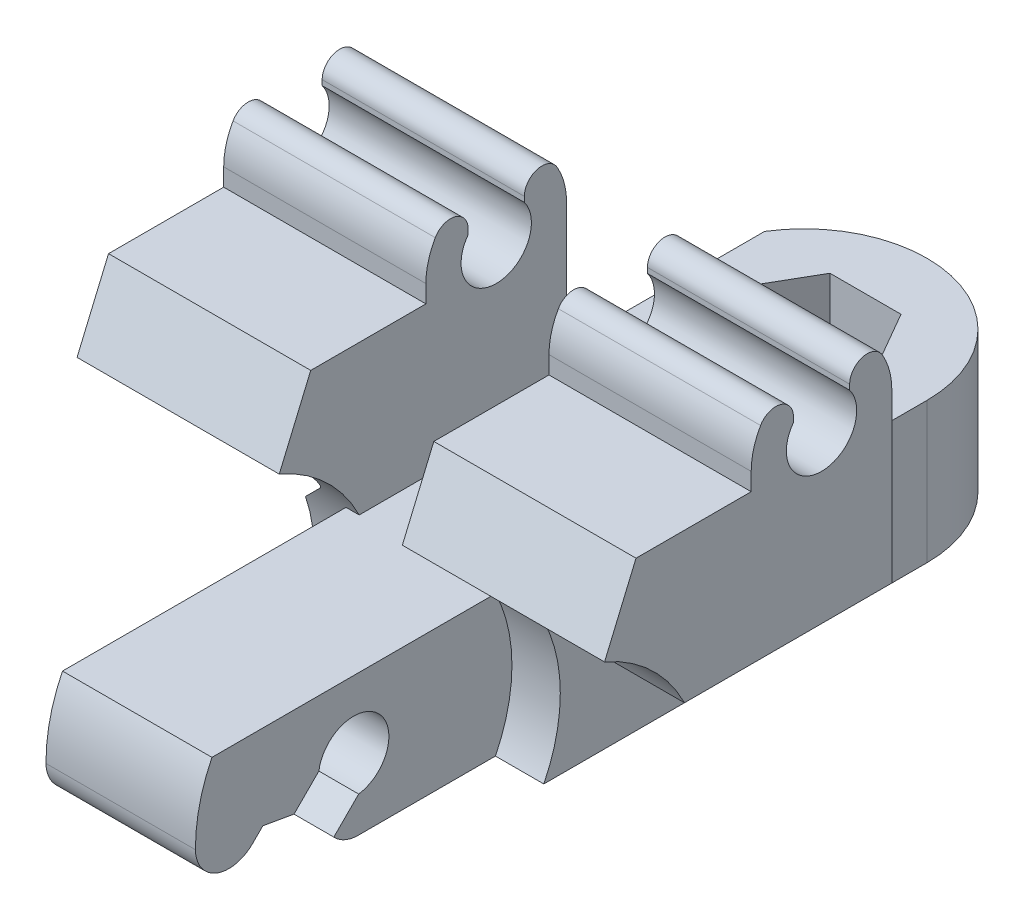
SolidWorks part; units mm, degrees
ref_plane "Front Plane" through (0, 0, 0) normal (0, 0, 1) x (1, 0, 0)
ref_plane "Top Plane" through (0, 0, 0) normal (0, 1, 0) x (1, 0, 0)
ref_plane "Right Plane" through (0, 0, 0) normal (1, 0, 0) x (0, 0, -1)
sketch "Sketch3" plane through (0, 0, 0) normal (1, 0, 0) x (0, 0, -1)
  line L0 (0.2828, -1.9799) -> (-1.9799, 0.2828)
  line L1 (0.2828, -1.9799) -> (-1.1314, -3.3941)
  line L2 (-1.1314, -3.3941) -> (-0.8188, -5.1668)
  line L3 (-0.8188, -5.1668) -> (-3.8071, -8.1551)
  line L4 (-1.9799, 0.2828) -> (-3.3941, -1.1314)
  line L5 (-3.3941, -1.1314) -> (-5.1668, -0.8188)
  line L6 (-5.1668, -0.8188) -> (-8.1551, -3.8071)
  line L7 (-0.8485, -0.8485) -> (0, 0) construction
  line L8 (0, 0) -> (-2, 0) construction
  line L9 (-1.9799, 0.2828) -> (-5.1668, -0.8188) construction
  line L10 (-0.8188, -5.1668) -> (0.2828, -1.9799) construction
  circle A0 centre (0, 0) radius 2
  circle A1 centre (0, 0) radius 8.5 construction
  circle A2 centre (0, 0) radius 9 construction
  circle A3 centre (0, 0) radius 9
  dimension "D1" = 4
  dimension "D2" = 17
  dimension "D3" = 7
  dimension "D4" = 0.5
  dimension "D5" = 2
  dimension "D7" = 3.2
  dimension "D6" = 1.8
  dimension "D8" = 45
  dimension "D9" = 125
extrude "Boss-Extrude1" add sketch "Sketch3" along normal mid plane 8.5 contours A3 L6 L5 L4 A0 L1 L2 L3 | A3 region at (0, -1.4772, -1.7032)
sketch "Sketch5" plane through (0, 0, 0) normal (1, 0, 0) x (0, 0, -1)
  line L0 (0, 9) -> (29.856, 9)
  line L1 (29.856, 9) -> (29.856, -9)
  line L2 (29.856, -9) -> (0, -9)
  arc A0 (-3.8071, -8.1551) -> (-8.1551, -3.8071) centre (0, 0) ccw construction
  arc A1 (0, -9) -> (0, 9) centre (0, 0) ccw
  dimension "D1" = 29.856
extrude "Boss-Extrude2" add sketch "Sketch5" along normal mid plane 14
sketch "Sketch6" plane through (0, 9, 0) normal (0, 1, 0) x (1, 0, 0)
  line L0 (7, 29.856) -> (-7, 29.856) construction
  circle A0 centre (0, 29.856) radius 7
extrude "Boss-Extrude3" add sketch "Sketch6" against normal up to surface (18 mm away) up to face at (0, -9, -9.952)
sketch "Sketch7" plane through (0, 0, 0) normal (0, 1, 0) x (1, 0, 0)
  circle A0 centre (0, 29.856) radius 4.5
  dimension "D1" = 9
extrude "Boss-Extrude4" add sketch "Sketch7" along normal blind 8 and the other way blind 8
sketch "Sketch8" plane through (0, 9, 0) normal (0, 1, 0) x (1, 0, 0)
  line L0 (4.25, -9) -> (4.25, 0) construction
  line L1 (-4.25, 0) -> (-4.25, -9) construction
  line L3 (7, 0) -> (7, 29.856) construction
  line L4 (-7, 29.856) -> (-7, 0) construction
  line L5 (-7, 0) -> (-4.25, 0) construction
  line L6 (4.25, 0) -> (7, 0) construction
  line L7 (4.25, -9) -> (4.25, 0)
  line L8 (-4.25, 0) -> (-4.25, -9)
  line L9 (-4.25, -9) -> (4.25, -9)
  line L10 (7, 0) -> (7, 29.856)
  line L11 (-7, 29.856) -> (-7, 0)
  line L12 (-7, 0) -> (-4.25, 0)
  line L13 (4.25, 0) -> (7, 0)
  arc A0 (7, 29.856) -> (-7, 29.856) centre (0, 29.856) ccw construction
  arc A1 (7, 29.856) -> (-7, 29.856) centre (0, 29.856) ccw
  line M10 (7, 0) -> (7, 29.856)
  arc M11 (7, 29.856) -> (-7, 29.856) centre (0, 29.856) ccw
  line M12 (-7, 29.856) -> (-7, 0)
  line M13 (-7, 0) -> (-4.25, 0)
  line M14 (-4.25, 0) -> (4.25, 0)
  line M15 (4.25, 0) -> (7, 0)
extrude "Cut-Extrude2" cut sketch "Sketch8" against normal offset from surface (5 mm away) 4 contours M15 M10 M11 M12 M13 M14 | L8 L9 L7 M14 region at (0, 9, 4.5) region at (0, 9, -17.7114) up to plane "Top Plane"
sketch "Sketch9" plane through (0, -9, 0) normal (0, -1, 0) x (1, 0, 0)
  line L7 (4.25, 0) -> (4.25, 9)
  line L8 (7, 0) -> (4.25, 0)
  line L9 (7, -29.856) -> (7, 0)
  line L10 (-7, 0) -> (-7, -29.856)
  line L11 (-4.25, 0) -> (-7, 0)
  line L12 (-4.25, 9) -> (-4.25, 0)
  line L13 (4.25, 9) -> (-4.25, 9)
  line L14 (4.25, 0) -> (4.25, 9)
  line L15 (7, 0) -> (4.25, 0)
  line L16 (7, -29.856) -> (7, 0)
  line L17 (-7, 0) -> (-7, -29.856)
  line L18 (-4.25, 0) -> (-7, 0)
  line L19 (-4.25, 9) -> (-4.25, 0)
  line L20 (4.25, 9) -> (-4.25, 9)
  arc A1 (-7, -29.856) -> (7, -29.856) centre (0, -29.856) ccw
  arc A2 (-7, -29.856) -> (7, -29.856) centre (0, -29.856) ccw
  line M10 (-7, 0) -> (-7, -29.856)
  arc M11 (-7, -29.856) -> (7, -29.856) centre (0, -29.856) ccw
  line M12 (7, -29.856) -> (7, 0)
  line M13 (7, 0) -> (4.25, 0)
  line M14 (4.25, 0) -> (-4.25, 0)
  line M15 (-4.25, 0) -> (-7, 0)
  dimension "D1" = 0
extrude "Cut-Extrude4" cut sketch "Sketch9" against normal offset from surface (5 mm away) 4 contours M15 M10 M11 M12 M13 M14 | L14 L20 L19 M14 region at (0, -9, 4.5) region at (0, -9, -17.7114) up to plane "Top Plane"
sketch "Sketch10" plane through (0, 0, 0) normal (1, 0, 0) x (0, 0, -1)
  line L3 (8.0623, -4) -> (29.856, -4)
  line L4 (29.856, -4) -> (29.856, 4)
  line L5 (29.856, 4) -> (8.0623, 4)
  line L10 (11.856, 12.5) -> (11.856, 17.5) construction
  line L11 (11.856, 17.5) -> (19.856, 17.5) construction
  line L12 (19.856, 17.5) -> (19.856, 4) construction
  line L13 (5.3059, 12.5) -> (11.856, 12.5)
  line L14 (0, 0) -> (3.5166, 8.2845) construction
  line L15 (3.5166, 8.2845) -> (5.3059, 12.5)
  line L16 (29.856, 4) -> (8.0623, 4) construction
  line L17 (19.856, 4) -> (8.0623, 4)
  line L18 (11.856, 13.5) -> (19.856, 13.5) construction
  line L19 (29.856, 14) -> (29.856, 4) construction
  line L21 (14.256, 14.7) -> (17.456, 14.7) construction
  line L22 (17.456, 14.7) -> (17.456, 17.1661)
  line L23 (14.256, 17.1661) -> (14.256, 14.7)
  line L24 (11.856, 13.5) -> (11.856, 12.5)
  line L25 (19.856, 13.5) -> (19.856, 4)
  arc A0 (14.256, 14.7) -> (17.456, 14.7) centre (15.856, 13.5) ccw
  arc A1 (8.0623, -4) -> (8.0623, 4) centre (0, 0) ccw
  arc A2 (8.0623, 4) -> (3.5166, 8.2845) centre (0, 0) ccw
  arc A3 (19.856, 13.5) -> (17.456, 17.1661) centre (15.856, 13.5) ccw
  arc A4 (14.256, 17.1661) -> (11.856, 13.5) centre (15.856, 13.5) ccw
  point P15 (0, 0)
  dimension "D8" = 4
  dimension "D9" = 2
  dimension "D10" = 3.2
  dimension "D2" = 67
  dimension "D3" = 10
  dimension "D4" = 13.5
  dimension "D5" = 5
  dimension "D7" = 5
  dimension "D1" = 0
extrude "Boss-Extrude5" add sketch "Sketch10" along normal mid plane 30
ref_plane "Plane1" through (6, 0, 0) normal (1, 0, 0) x (0, 0, -1)
ref_plane "Plane2" through (-6, 0, 0) normal (1, 0, 0) x (0, 0, -1)
sketch "Sketch13" plane through (-6, 0, 0) normal (1, 0, 0) x (0, 0, -1)
  line L0 (0, 5) -> (36.856, 5)
  line L2 (36.856, 4) -> (36.856, 5) construction
  circle A0 centre (0, 0) radius 5 construction
  dimension "D1" = 10
ref_plane "Plane3" through (0, 0, 0) normal (0, 0, 1) x (1, 0, 0)
sketch "Sketch14" plane through (0, 0, 0) normal (0, 0, 1) x (1, 0, 0)
  line L0 (-6.5303, 5.5303) -> (-8.0607, 4)
  line L1 (-7, 4) -> (-15, 4) construction
  line L2 (-5.4697, 4.4697) -> (-7, 2.9393)
  line L3 (-7, 4) -> (-7, -4) construction
  line L4 (-6.5303, 5.5303) -> (-5.4697, 4.4697) construction
  line L5 (-8.0607, 4) -> (-7, 4)
  line L6 (-7, 4) -> (-7, 2.9393)
  arc A0 (-5.4697, 4.4697) -> (-6.5303, 5.5303) centre (-6, 5) ccw
  point P14 (-6, 5)
  dimension "D1" = 1.5
  dimension "D2" = 45
sweep "Cut-Sweep1" cut profiles "Sketch14" path "Sketch13"
ref_plane "Plane4" [suppressed] through (0, 0, -32.856) normal (0, 0, -1) x (-1, 0, 0)
ref_plane "Plane5" [suppressed] through (-3, 0, 0) normal (-1, 0, 0) x (0, 0, 1)
sketch "Sketch18" [suppressed] plane through (0, 0, -32.856) normal (0, 0, -1) x (-1, 0, 0)
  line L0 (0, 29) -> (0, 16) construction
  line L2 (3, 29) -> (-3, 29) construction
  circle A0 centre (0, 16) radius 1.9
  dimension "D2" = 3.8
  dimension "D1" = 13
extrude "Cut-Extrude5" [suppressed] cut sketch "Sketch18" against normal blind 1
sketch "Sketch20" plane through (0, 4, 0) normal (0, 1, 0) x (1, 0, 0)
  line L0 (0, 25.356) -> (0, 0) construction
  line L2 (-3.5, -19.856) -> (3.5, -19.856)
  line L3 (-3.5, -19.856) -> (-3.5, 19.856)
  line L4 (-3.5, 19.856) -> (3.5, 19.856)
  line L5 (3.5, -19.856) -> (3.5, 19.856)
  line L6 (-3.5, -19.856) -> (3.5, 19.856) construction
  line L7 (-3.5, 19.856) -> (3.5, -19.856) construction
  line L8 (-5.9393, 19.856) -> (7, 19.856) construction
  point P4 (0, 0)
  point P11 (0, 0)
  dimension "D1" = 7
extrude "Cut-Extrude7" cut sketch "Sketch20" along normal through all
fillet "Fillet1" radius 1.9 2 edges at (0, -3.8071, 8.1551) (0, -4, 1.0245)
fillet "Fillet2" radius 1 4 edges at (-9.25, 17.1661, -17.456) (-9.25, 17.1661, -14.256) (9.25, 17.1661, -14.256) (9.25, 17.1661, -17.456)
sketch "Sketch23" plane through (0, 4, 0) normal (0, 1, 0) x (1, 0, 0)
  line L0 (-7, 29.856) -> (7, 29.856) construction
  line L1 (4.0415, 29.856) -> (2.0207, 33.356)
  line L2 (2.0207, 33.356) -> (-2.0207, 33.356)
  line L3 (-2.0207, 33.356) -> (-4.0415, 29.856)
  line L4 (-4.0415, 29.856) -> (-2.0207, 26.356)
  line L5 (-2.0207, 26.356) -> (2.0207, 26.356)
  line L6 (2.0207, 26.356) -> (4.0415, 29.856)
  circle A0 centre (0, 29.856) radius 3.5 construction
  point P1 (0, 29.856)
  dimension "D1" = 7
extrude "Cut-Extrude8" cut sketch "Sketch23" against normal through all
